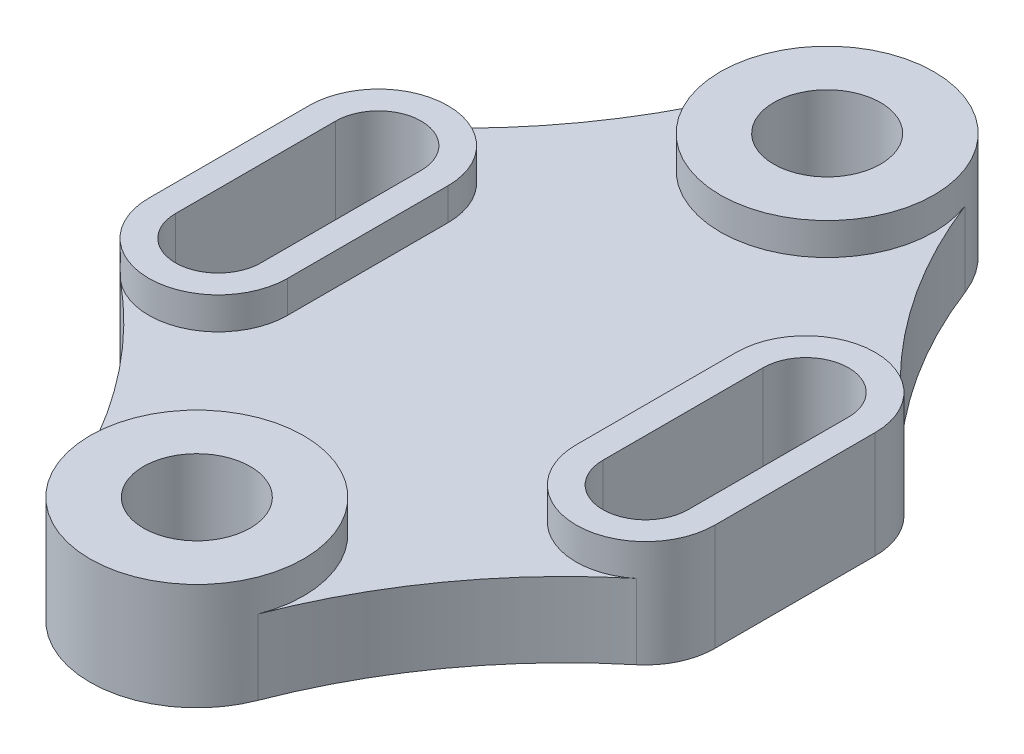
SolidWorks part; units mm, degrees
material "AISI 4130 Steel, normalized at 870C"
ref_plane "Front Plane" through (0, 0, 0) normal (0, 0, 1) x (1, 0, 0)
ref_plane "Top Plane" through (0, 0, 0) normal (0, 1, 0) x (1, 0, 0)
ref_plane "Right Plane" through (0, 0, 0) normal (1, 0, 0) x (0, 0, -1)
sketch "Sketch1" plane through (0, 0, 0) normal (0, 1, 0) x (1, 0, 0)
  line L0 (-40, -15) -> (-40, 15) construction
  line L1 (-48, -15) -> (-48, 15)
  line L2 (-32, -15) -> (-32, 15)
  line L3 (40, -15) -> (40, 15) construction
  line L4 (32, -15) -> (32, 15)
  line L5 (48, -15) -> (48, 15)
  line L6 (27, -15) -> (27, 15)
  line L7 (53, -15) -> (53, 15)
  line L8 (-53, -15) -> (-53, 15)
  line L9 (-27, -15) -> (-27, 15)
  line L10 (-7.2651, 0) -> (7.2651, 0) construction
  circle A0 centre (0, 59) radius 10
  circle A1 centre (0, 59) radius 20
  arc A2 (-48, -15) -> (-32, -15) centre (-40, -15) ccw
  arc A3 (-32, 15) -> (-48, 15) centre (-40, 15) ccw
  arc A4 (32, -15) -> (48, -15) centre (40, -15) ccw
  arc A5 (48, 15) -> (32, 15) centre (40, 15) ccw
  arc A6 (53, 15) -> (27, 15) centre (40, 15) ccw
  arc A7 (27, -15) -> (53, -15) centre (40, -15) ccw
  arc A8 (-27, 15) -> (-53, 15) centre (-40, 15) ccw
  arc A9 (-53, -15) -> (-27, -15) centre (-40, -15) ccw
  arc A10 (-18.6657, 66.1828) -> (-48.2825, 25.02) centre (-111.994, 102.0968) cw
  arc A11 (18.6657, 66.1828) -> (48.2825, 25.02) centre (111.994, 102.0968) ccw
  arc A12 (18.6657, -66.1828) -> (48.2825, -25.02) centre (111.994, -102.0968) cw
  arc A13 (-18.6657, -66.1828) -> (-48.2825, -25.02) centre (-111.994, -102.0968) ccw
  circle A14 centre (0, -59) radius 20
  circle A15 centre (0, -59) radius 10
  point P5 (-40, 0)
  point P10 (40, 0)
  point P35 (0, 0)
  point P37 (0, 0)
  point P38 (0, 0)
  point P39 (0, 0)
  point P40 (0, 0)
  point P41 (0, 0)
  point P42 (-20, 74)
  point P54 (0, 0)
  point P55 (0, 0)
  dimension "D2" = 20
  dimension "40" = 40
  dimension "D6" = 8
  dimension "D7" = 44
  dimension "D8" = 100
  dimension "D3" = 80
  dimension "D4" = 40
  dimension "D5" = 30
  dimension "D1" = 5
extrude "Boss-Extrude1" add sketch "Sketch1" along normal blind 14 contours A13 A14 A12 A7 L6 A6 A11 A1 A10 A8 L9 A9 region at (0, 0, 0)
extrude "Boss-Extrude2" add sketch "Sketch1<3>" along normal blind 20 contours A14 A15 | L8 A9 L9 A8 A3 L2 A2 L1 | L6 A7 L7 A6 A5 L5 A4 L4 | A1 A0 region at (27.6174, 0, 0) region at (0, 0, 78.4343) region at (19.1074, 0, -62.5495) region at (-51.203, 0, 20.2745)
sketch "Sketch1<3>" plane through (0, 0, 0) normal (0, 1, 0) x (1, 0, 0) same geometry as "Sketch1"
